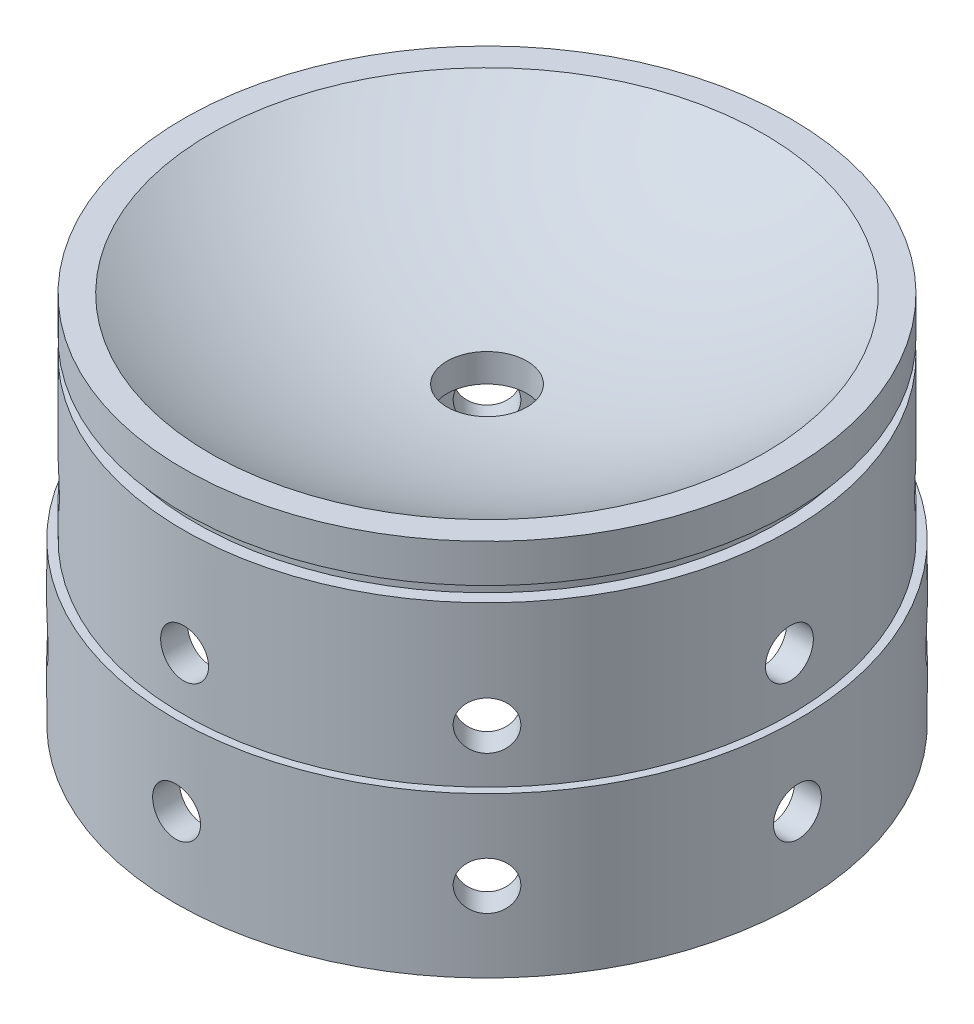
SolidWorks part; units mm, degrees
material "6061-T6 (SS)"
ref_plane "Front Plane" through (0, 0, 0) normal (0, 0, 1) x (1, 0, 0)
ref_plane "Top Plane" through (0, 0, 0) normal (0, 1, 0) x (1, 0, 0)
ref_plane "Right Plane" through (0, 0, 0) normal (1, 0, 0) x (0, 0, -1)
sketch "Sketch1" plane through (0, 0, 0) normal (0, 0, 1) x (1, 0, 0)
  line L0 (0, 0) -> (0, 6.35)
  line L1 (0, 0) -> (72.39, 0)
  line L2 (72.39, 0) -> (72.39, 12.7)
  line L3 (72.39, 12.7) -> (69.469, 12.7)
  line L4 (69.469, 12.7) -> (69.469, 16.256)
  line L5 (69.469, 16.256) -> (72.39, 16.256)
  line L6 (72.39, 16.256) -> (72.39, 25.4)
  line L9 (72.39, 6.35) -> (0, 6.35) construction
  line L10 (72.39, 0) -> (72.39, -25.4)
  line L11 (72.39, -25.4) -> (66.04, -25.4)
  line L12 (66.04, -25.4) -> (66.04, 0)
  line L13 (74.93, 68.1653) -> (74.93, 53.6699) construction
  line L14 (67.945, -63.5) -> (67.945, -25.4)
  line L15 (67.945, -63.5) -> (74.295, -63.5)
  line L16 (9.525, 6.7164) -> (9.525, 0)
  line L17 (73.025, 45.3691) -> (73.025, 21.7883) construction
  line L18 (74.295, -63.5) -> (74.295, -25.4)
  line L19 (74.295, -25.4) -> (72.39, -25.4)
  line L20 (72.39, 25.4) -> (66.04, 25.4)
  arc A1 (0, 6.35) -> (66.04, 25.4) centre (0, 130.3443) ccw
  dimension "D1" = 72.39
  dimension "D9" = 6.35
  dimension "D12" = 9.525
  dimension "D3" = 12.7
  dimension "D4" = 3.556
  dimension "D2" = 73.025
  dimension "D13" = 3.556
  dimension "D6" = 6.35
  dimension "D7" = 25.4
  dimension "D8" = 74.93
  dimension "D10" = 38.1
  dimension "D11" = 74.295
  dimension "D5" = 25.4
  dimension "D14" = 6.35
revolve "Revolve1" add sketch "Sketch1" angle 360 about L0 region at (48.3195, 8.6296, 0) region at (69.215, -12.7, 0) region at (71.12, -44.45, 0)
hole_wizard "1/2 (0.45) Diameter Hole3" positions "3DSketch5" profile "Sketch8" hole size "1/2" standard "ANSI Inch"
sketch3d "3DSketch5"
  line L0 (0, -25.4, 0) -> (0, 0, 0) construction
  line L2 (0, -12.7, 0) -> (72.39, -12.7, 0)
  circle A8 centre (0, -25.4, 0) radius 72.39 construction
  circle A9 centre (0, -25.4, 0) radius 72.39
  point P0 (72.39, -12.7, 0)
  point P41 (0, -97.79, 0)
  point P43 (0, -97.79, 0)
  point P53 (72.39, -12.7, 0)
sketch "Sketch8" plane through (72.39, -12.7, 0) normal (0, 1, 0) x (0, 0, -1)
  line L0 (0, 0) -> (0, 75.8229)
  line L1 (0, 75.8229) -> (5.715, 72.389)
  line L2 (5.715, 72.389) -> (5.715, 0)
  line L5 (5.715, 0) -> (0, 0)
  line L10 (0, 75.8229) -> (-5.715, 72.389) construction
  line L11 (0, -6.35) -> (0, 107.95) construction
  dimension "Hole Dia." = 11.43
  dimension "Hole Depth" = 72.389
  dimension "Drill Angle" = 118
hole_wizard "1/2 (0.45) Diameter Hole2" positions "3DSketch6" profile "Sketch9" hole size "1/2" standard "ANSI Inch"
sketch3d "3DSketch6"
  line L0 (0, -25.4, 0) -> (0, -63.5, 0)
  line L2 (0, -44.45, 0) -> (74.295, -44.45, 0)
  circle A0 centre (0, -63.5, 0) radius 74.295 construction
  circle A1 centre (0, -25.4, 0) radius 74.295 construction
  circle A2 centre (0, -63.5, 0) radius 74.295
  circle A3 centre (0, -25.4, 0) radius 74.295
  point P0 (74.295, -44.45, 0)
  point P5 (0, -137.795, 0)
  point P8 (0, -99.695, 0)
  point P10 (0, -137.795, 0)
  point P12 (0, -99.695, 0)
sketch "Sketch9" plane through (74.295, -44.45, 0) normal (0, 1, 0) x (0, 0, -1)
  line L0 (0, 0) -> (0, 77.7279)
  line L1 (0, 77.7279) -> (5.715, 74.294)
  line L2 (5.715, 74.294) -> (5.715, 0)
  line L5 (5.715, 0) -> (0, 0)
  line L10 (0, 77.7279) -> (-5.715, 74.294) construction
  line L11 (0, -6.35) -> (0, 107.95) construction
  dimension "Hole Dia." = 11.43
  dimension "Hole Depth" = 74.294
  dimension "Drill Angle" = 118
ref_axis "CenterAxis" through (0, 6.7164, 0) along (0, -1, 0)
chamfer "Chamfer1" distance 2.54 angle 45 1 edges at (0, -25.4, -67.945)
pattern_circular "CirPattern1" count 8 over 360 about axis through (0, -25.4, 0) along (0, -1, 0) of "1/2 (0.45) Diameter Hole3", "1/2 (0.45) Diameter Hole2"
equation "\"D1@Sketch1\"=(5.75/2)-(0.025in)"
equation "\"D12@Sketch1\"=0.75/2"
equation "\"D2@Sketch1\"=5.75/2"
equation "\"D8@Sketch1\"=5.9/2"
equation "\"D11@Sketch1\"=5.9/2 - (0.025in)"
